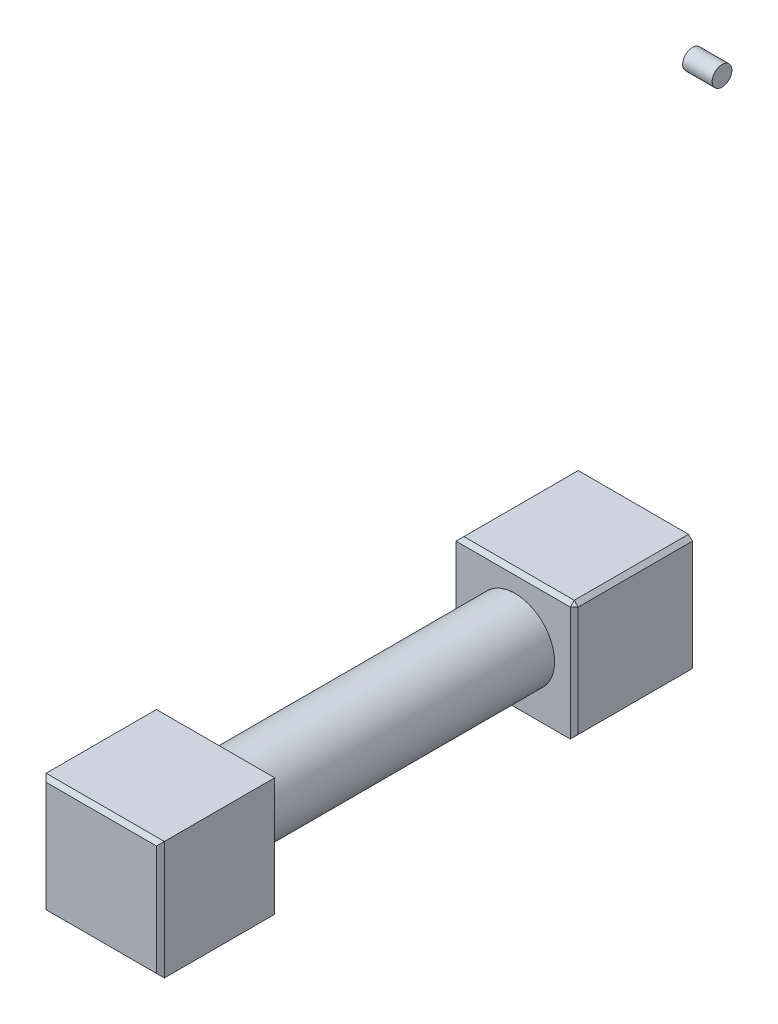
SolidWorks part; units mm, degrees
ref_plane "前视基准面" through (0, 0, 0) normal (0, 0, 1) x (1, 0, 0)
ref_plane "上视基准面" through (0, 0, 0) normal (0, 1, 0) x (1, 0, 0)
ref_plane "右视基准面" through (0, 0, 0) normal (1, 0, 0) x (0, 0, -1)
other "Configuration Table"
sketch "Sketch1" plane through (0, 0, 0) normal (0, 0, 1) x (1, 0, 0)
  line L1 (-30, -30) -> (30, -30)
  line L2 (-30, -30) -> (-30, 30)
  line L3 (-30, 30) -> (30, 30)
  line L4 (30, -30) -> (30, 30)
  line L5 (-30, -30) -> (30, 30) construction
  line L6 (-30, 30) -> (30, -30) construction
  point P0 (0, 0)
extrude "Boss-Extrude1" add sketch "Sketch1" along normal blind 60
sketch "Sketch2" plane through (0, 0, 0) normal (0, 0, 1) x (1, 0, 0)
  circle A0 centre (0, 0) radius 20
extrude "Cut-Extrude1" cut sketch "Sketch2" along normal blind 61
ref_plane "Plane1" through (0, 0, 60) normal (0, 0, 1) x (1, 0, 0)
sketch "Sketch3" plane through (0, 0, 60) normal (0, 0, 1) x (1, 0, 0)
  circle A0 centre (0, 0) radius 20
extrude "Boss-Extrude2" add sketch "Sketch3" along normal blind 150
ref_plane "Plane2" through (0, 0, 210) normal (0, 0, 1) x (1, 0, 0)
sketch "Sketch4" plane through (0, 0, 210) normal (0, 0, 1) x (1, 0, 0)
  line L1 (-30, -30) -> (30, -30)
  line L2 (-30, -30) -> (-30, 30)
  line L3 (-30, 30) -> (30, 30)
  line L4 (30, -30) -> (30, 30)
  line L5 (-30, -30) -> (30, 30) construction
  line L6 (-30, 30) -> (30, -30) construction
  point P0 (0, 0)
extrude "Boss-Extrude3" add sketch "Sketch4" along normal blind 60
chamfer "Chamfer1" distance 2 angle 45 6 edges at (-30, -30, 30) (-30, 30, 30) (30, -30, 30) (30, 30, 30) (30, 0, 60) (0, 30, 60)
chamfer "Chamfer3" distance 2 angle 45 7 edges at (0, -30, 270) (-30, 0, 270) (0, 30, 270) (30, 0, 270) (-30, 0, 210) (0, 30, 210) (30, 0, 210)
ref_plane "Plane3" through (30, 0, 0) normal (1, 0, 0) x (0, 0, -1)
sketch "Sketch5" plane through (30, 0, 0) normal (1, 0, 0) x (0, 0, -1)
  circle A0 centre (0, 240) radius 5
extrude "Boss-Extrude4" add sketch "Sketch5" along normal blind 15
sketch3d "3DSketch1"
  line L0 (0, 0, 0) -> (0, 0, 1000) construction
ref_axis "central_hole_axis" through (0, 0, 0) along (0, 0, 1)
sketch3d "3DSketch2"
  line L0 (30, 0, 240) -> (40, 0, 240) construction
ref_axis "pin_axis" through (30, 0, 240) along (1, 0, 0)
ref_plane "bottom_face" through (0, 0, 0) normal (0, 0, 1) x (1, 0, 0)
ref_plane "top_pin_face" through (30, 0, 0) normal (1, 0, 0) x (0, 0, -1)
ref_plane "side_mate_face_top" through (30, 0, 0) normal (1, 0, 0) x (0, 0, -1)
